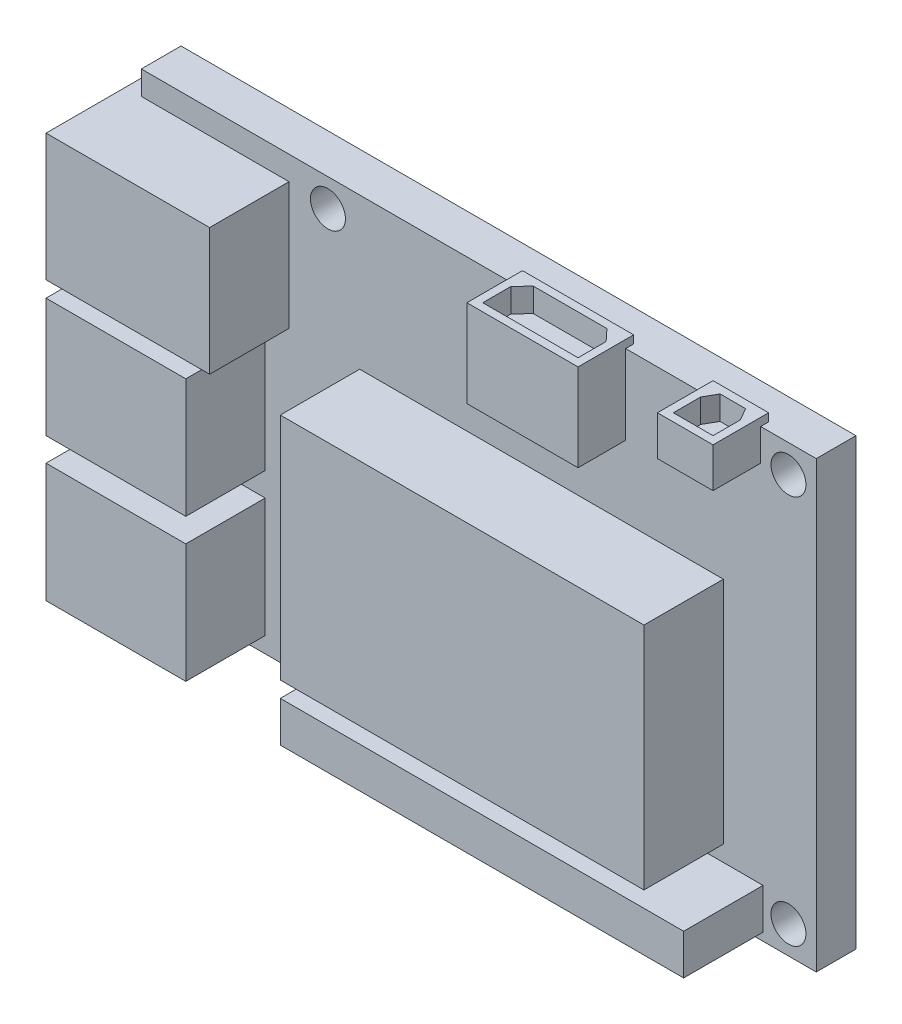
SolidWorks part; units mm, degrees
ref_plane "Alzado" through (0, 0, 0) normal (0, 0, 1) x (1, 0, 0)
ref_plane "Planta" through (0, 0, 0) normal (0, 1, 0) x (1, 0, 0)
ref_plane "Vista lateral" through (0, 0, 0) normal (1, 0, 0) x (0, 0, -1)
sketch "Croquis1" plane through (0, 0, 0) normal (0, 0, 1) x (1, 0, 0)
  line L1 (0, 56) -> (85, 56)
  line L2 (0, 56) -> (0, 0)
  line L3 (0, 0) -> (85, 0)
  line L4 (85, 56) -> (85, 0)
  circle A0 centre (23.5, 52.5) radius 2.2
  circle A1 centre (23.5, 3.5) radius 2.2
  circle A2 centre (81.5, 52.5) radius 2.2
  circle A3 centre (81.5, 3.5) radius 2.2
  dimension "D1" = 56
  dimension "D2" = 85
  dimension "D11" = 23.5
  dimension "D12" = 3.5
  dimension "D13" = 3.5
  dimension "D14" = 3.5
extrude "Saliente-Extruir3" add sketch "Croquis1" along normal blind 5
sketch "Croquis2" plane through (0, 0, 5) normal (0, 0, 1) x (1, 0, 0)
  line L0 (0, 56) -> (0, 0) construction
  line L1 (-2, 53) -> (18.6, 53)
  line L2 (-2, 53) -> (-2, 37)
  line L3 (-2, 37) -> (18.6, 37)
  line L4 (18.6, 53) -> (18.6, 37)
  line L5 (85, 56) -> (0, 56) construction
  dimension "D1" = 20.6
  dimension "D2" = 16
  dimension "D3" = 2
  dimension "D4" = 3
extrude "Saliente-Extruir4" add sketch "Croquis2" along normal blind 10 and the other way blind 3
sketch "Croquis3" plane through (0, 0, 5) normal (0, 0, 1) x (1, 0, 0)
  line L1 (27.5, 6.1) -> (78.3, 6.1)
  line L2 (27.5, 6.1) -> (27.5, 1)
  line L3 (27.5, 1) -> (78.3, 1)
  line L4 (78.3, 6.1) -> (78.3, 1)
  line L5 (85, 0) -> (85, 56) construction
  line L6 (0, 0) -> (85, 0) construction
  dimension "D1" = 50.8
  dimension "D2" = 5.1
  dimension "D3" = 6.7
  dimension "D4" = 1
extrude "Saliente-Extruir5" add sketch "Croquis3" along normal blind 10
sketch "Croquis4" plane through (-2, 0, 0) normal (-1, 0, 0) x (0, 0, 1)
  line L0 (15, 53) -> (15, 37) construction
  line L1 (3, 52) -> (14, 52)
  line L2 (3, 52) -> (3, 38)
  line L3 (3, 38) -> (14, 38)
  line L4 (14, 52) -> (14, 38)
  line L5 (2, 53) -> (2, 37) construction
  line L6 (2, 53) -> (15, 53) construction
  line L7 (2, 37) -> (15, 37) construction
  dimension "D1" = 1
  dimension "D2" = 1
  dimension "D3" = 1
  dimension "D4" = 1
extrude "Cortar-Extruir2" cut sketch "Croquis4" against normal blind 15
sketch "Croquis5" plane through (0, 0, 5) normal (0, 0, 1) x (1, 0, 0)
  line L1 (27.5, 37) -> (73.3, 37)
  line L2 (27.5, 37) -> (27.5, 8.1)
  line L3 (27.5, 8.1) -> (73.3, 8.1)
  line L4 (73.3, 37) -> (73.3, 8.1)
  line L6 (27.5, 6.1) -> (27.5, 1) construction
  line L7 (78.3, 1) -> (78.3, 6.1) construction
  line L8 (78.3, 6.1) -> (27.5, 6.1) construction
  line L9 (0, 37) -> (18.6, 37) construction
  dimension "D1" = 5
  dimension "D2" = 2
extrude "Saliente-Extruir6" add sketch "Croquis5" along normal blind 10
sketch "Croquis6" plane through (0, 0, 5) normal (0, 0, 1) x (1, 0, 0)
  line L0 (-2, 53) -> (-2, 37) construction
  line L1 (-2, 35) -> (15.6, 35)
  line L2 (-2, 35) -> (-2, 20)
  line L3 (-2, 20) -> (15.6, 20)
  line L4 (15.6, 35) -> (15.6, 20)
  line L5 (18.6, 37) -> (18.6, 53) construction
  line L6 (0, 37) -> (18.6, 37) construction
  line L8 (-2, 17) -> (15.6, 17)
  line L9 (-2, 17) -> (-2, 2)
  line L10 (-2, 2) -> (15.6, 2)
  line L11 (15.6, 17) -> (15.6, 2)
  dimension "D1" = 3
  dimension "D2" = 2
  dimension "D3" = 15
  dimension "D4" = 15
  dimension "D5" = 3
extrude "Saliente-Extruir8" add sketch "Croquis6" along normal blind 10 and the other way blind 3
sketch "Croquis7" plane through (-2, 0, 0) normal (-1, 0, 0) x (0, 0, 1)
  line L1 (3, 34) -> (8, 34)
  line L2 (3, 34) -> (3, 21)
  line L3 (3, 21) -> (8, 21)
  line L4 (8, 34) -> (8, 21)
  line L6 (2, 35) -> (15, 35) construction
  line L7 (2, 20) -> (15, 20) construction
  line L8 (2, 35) -> (2, 20) construction
  line L9 (15, 35) -> (15, 20) construction
  line L10 (9, 34) -> (14, 34)
  line L11 (9, 34) -> (9, 21)
  line L12 (9, 21) -> (14, 21)
  line L13 (14, 34) -> (14, 21)
  line L14 (2, 17) -> (15, 17) construction
  line L15 (14, 16) -> (9, 16)
  line L16 (14, 16) -> (14, 3)
  line L17 (14, 3) -> (9, 3)
  line L18 (9, 16) -> (9, 3)
  line L19 (2, 2) -> (15, 2) construction
  line L21 (8, 16) -> (3, 16)
  line L22 (8, 16) -> (8, 3)
  line L23 (8, 3) -> (3, 3)
  line L24 (3, 16) -> (3, 3)
  dimension "D1" = 5
  dimension "D2" = 1
  dimension "D3" = 1
  dimension "D4" = 1
  dimension "D5" = 1
  dimension "D6" = 5
  dimension "D7" = 1
  dimension "D8" = 1
extrude "Cortar-Extruir3" cut sketch "Croquis7" against normal blind 15
sketch "Croquis8" plane through (0, 0, 5) normal (0, 0, 1) x (1, 0, 0)
  line L0 (85, 0) -> (85, 56) construction
  line L1 (71, 57) -> (78, 57)
  line L2 (71, 57) -> (71, 52)
  line L3 (71, 52) -> (78, 52)
  line L4 (78, 57) -> (78, 52)
  line L5 (85, 56) -> (0, 56) construction
  line L7 (47, 57) -> (61, 57)
  line L8 (47, 57) -> (47, 46)
  line L9 (47, 46) -> (61, 46)
  line L10 (61, 57) -> (61, 46)
  dimension "D1" = 7
  dimension "D2" = 7
  dimension "D3" = 5
  dimension "D4" = 1
  dimension "D5" = 24
  dimension "D6" = 14
  dimension "D7" = 11
  dimension "D8" = 1
extrude "Saliente-Extruir9" add sketch "Croquis8" along normal blind 6 and the other way blind 1
sketch "Croquis9" plane through (0, 57, 0) normal (0, 1, 0) x (1, 0, 0)
  line L0 (48, -10) -> (60, -10)
  line L1 (60, -10) -> (60, -6.4621)
  line L2 (60, -6.4621) -> (58.6354, -5)
  line L3 (58.6354, -5) -> (49.3646, -5)
  line L4 (49.3646, -5) -> (48, -6.4621)
  line L5 (48, -6.4621) -> (48, -10)
  line L6 (61, -11) -> (47, -11) construction
  line L7 (61, -4) -> (47, -4) construction
  line L8 (47, -4) -> (47, -11) construction
  line L9 (61, -4) -> (61, -11) construction
  line L10 (72, -10) -> (77, -10)
  line L11 (77, -10) -> (77, -6.5618)
  line L12 (77, -6.5618) -> (76.1052, -5)
  line L13 (76.1052, -5) -> (72.8948, -5)
  line L14 (72.8948, -5) -> (72, -6.5618)
  line L15 (72, -6.5618) -> (72, -10)
  line L16 (78, -4) -> (71, -4) construction
  line L17 (71, -4) -> (71, -11) construction
  line L18 (78, -4) -> (78, -11) construction
  point P2 (54, -11)
  point P27 (0, 0)
  dimension "D1" = 2
  dimension "D2" = 2
  dimension "D3" = 1
  dimension "D4" = 1
  dimension "D5" = 3.5379
  dimension "D6" = 1
  dimension "D7" = 1
  dimension "D8" = 1.8
  dimension "D9" = 1.8
  dimension "D10" = 1
  dimension "D11" = 1
  dimension "D12" = 1
  dimension "D13" = 3.2103
extrude "Cortar-Extruir4" cut sketch "Croquis9" against normal blind 3
